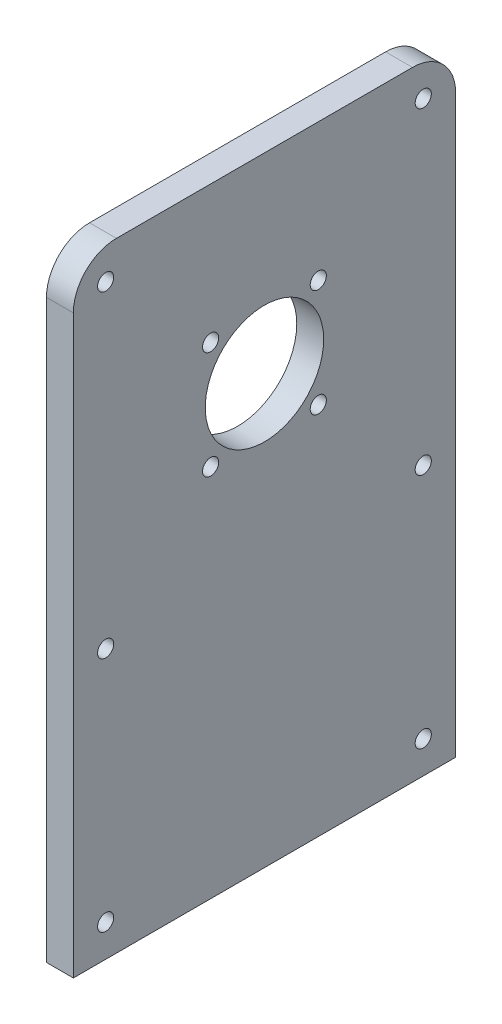
SolidWorks part; units mm, degrees
ref_plane "Front Plane" through (0, 0, 0) normal (0, 0, 1) x (1, 0, 0)
ref_plane "Top Plane" through (0, 0, 0) normal (0, 1, 0) x (1, 0, 0)
ref_plane "Right Plane" through (0, 0, 0) normal (1, 0, 0) x (0, 0, -1)
sketch "Sketch1" plane through (0, 0, 0) normal (1, 0, 0) x (0, 0, -1)
  line L1 (0, 0) -> (71, 0)
  line L2 (0, 0) -> (0, 115)
  line L3 (0, 115) -> (71, 115)
  line L4 (71, 0) -> (71, 115)
  circle A0 centre (6, 109) radius 1.5
  circle A1 centre (65, 109) radius 1.5
  circle A2 centre (35.5, 79.5) radius 11
  circle A3 centre (25.5, 89.5) radius 1.5
  circle A4 centre (45.5, 89.5) radius 1.5
  circle A5 centre (45.5, 69.5) radius 1.5
  circle A6 centre (25.5, 69.5) radius 1.5
  circle A7 centre (6, 50) radius 1.5
  circle A8 centre (65, 50) radius 1.5
  circle A9 centre (6, 6) radius 1.5
  circle A10 centre (65, 6) radius 1.5
  dimension "D3" = 3
  dimension "D7" = 22
  dimension "D14" = 3
  dimension "D1" = 71
  dimension "D2" = 115
  dimension "D4" = 6
  dimension "D5" = 6
  dimension "D6" = 6
  dimension "D8" = 35.5
  dimension "D9" = 35.5
  dimension "D10" = 20
  dimension "D11" = 10
  dimension "D12" = 10
  dimension "D13" = 20
  dimension "D15" = 59
  dimension "D16" = 6
extrude "Boss-Extrude1" add sketch "Sketch1" along normal blind 5
fillet "Fillet1" radius 8 2 edges at (2.5, 115, -71) (2.5, 115, 0)
